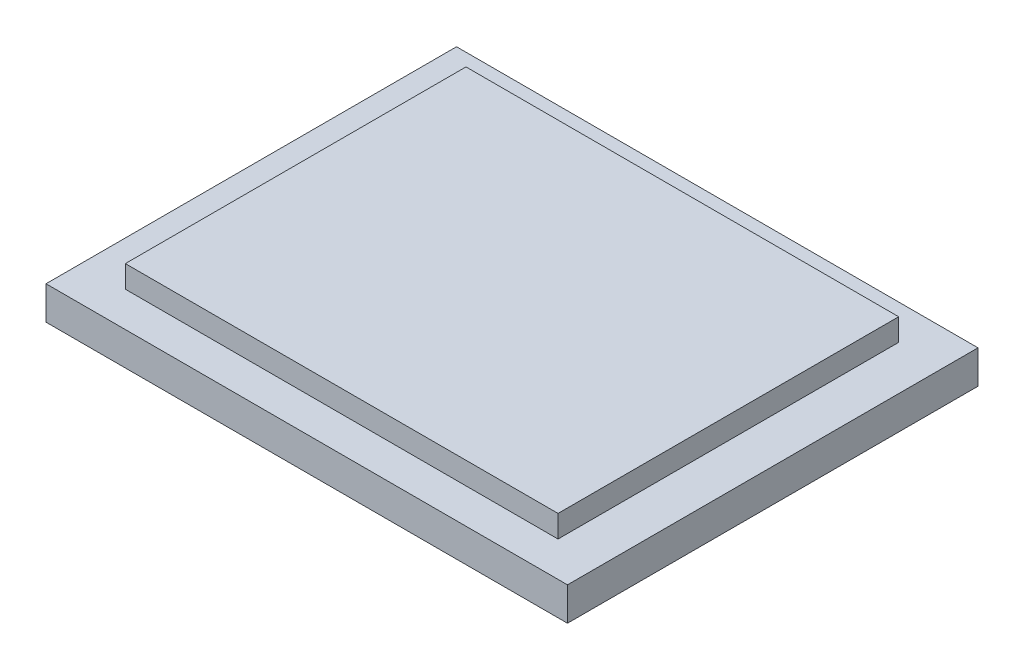
SolidWorks part; units mm, degrees
ref_plane "Front Plane" through (0, 0, 0) normal (0, 0, 1) x (1, 0, 0)
ref_plane "Top Plane" through (0, 0, 0) normal (0, 1, 0) x (1, 0, 0)
ref_plane "Right Plane" through (0, 0, 0) normal (1, 0, 0) x (0, 0, -1)
sketch "Sketch2" plane through (0, 0, 0) normal (0, 1, 0) x (1, 0, 0)
  line L1 (-29.845, -23.495) -> (29.845, -23.495)
  line L2 (-29.845, -23.495) -> (-29.845, 23.495)
  line L3 (-29.845, 23.495) -> (29.845, 23.495)
  line L4 (29.845, -23.495) -> (29.845, 23.495)
  line L5 (-29.845, -23.495) -> (29.845, 23.495) construction
  line L6 (-29.845, 23.495) -> (29.845, -23.495) construction
  line L7 (-24.765, -19.4959) -> (24.765, -19.4959)
  line L8 (-24.765, -19.4959) -> (-24.765, 19.4959)
  line L9 (-24.765, 19.4959) -> (24.765, 19.4959)
  line L10 (24.765, -19.4959) -> (24.765, 19.4959)
  line L11 (-24.765, -19.4959) -> (24.765, 19.4959) construction
  line L12 (-24.765, 19.4959) -> (24.765, -19.4959) construction
  point P0 (0, 0)
  point P6 (0, 0)
  dimension "D1" = 59.69
  dimension "D2" = 46.99
  dimension "D3" = 49.53
extrude "Boss-Extrude1" add sketch "Sketch2" along normal blind 3.81 contours L7 L10 L9 L8 | L1 L4 L3 L2 L10 L7 L8 L9 region at (-29.0853, 0, 0) region at (0, 0, 0)
extrude "Boss-Extrude2" add sketch "Sketch2<3>" along normal blind 6.35 contours L7 L10 L9 L8 region at (0, 0, 0)
sketch "Sketch2<3>" plane through (0, 0, 0) normal (0, 1, 0) x (1, 0, 0) same geometry as "Sketch2"
sketch "Sketch4" plane through (0, 0, 0) normal (0, -1, 0) x (1, 0, 0)
  line L0 (-29.845, 7.62) -> (29.845, 7.62) construction
  line L1 (-29.845, 23.495) -> (-29.845, -23.495) construction
  line L2 (29.845, 23.495) -> (29.845, -23.495) construction
  line L3 (-29.845, 0) -> (29.845, 0) construction
  line L4 (-29.845, -7.62) -> (29.845, -7.62) construction
  text T0 "IGNITER CONTROLLER"
  text T1 "DEFLAGRATION RESEARCH LAB" font "Century Gothic" height in points 10
  text T2 "IAN'S A NERD"
  dimension "D1" = 7.62
  dimension "D2" = 7.62
extrude "Cut-Extrude1" cut sketch "Sketch4" against normal blind 0.635
